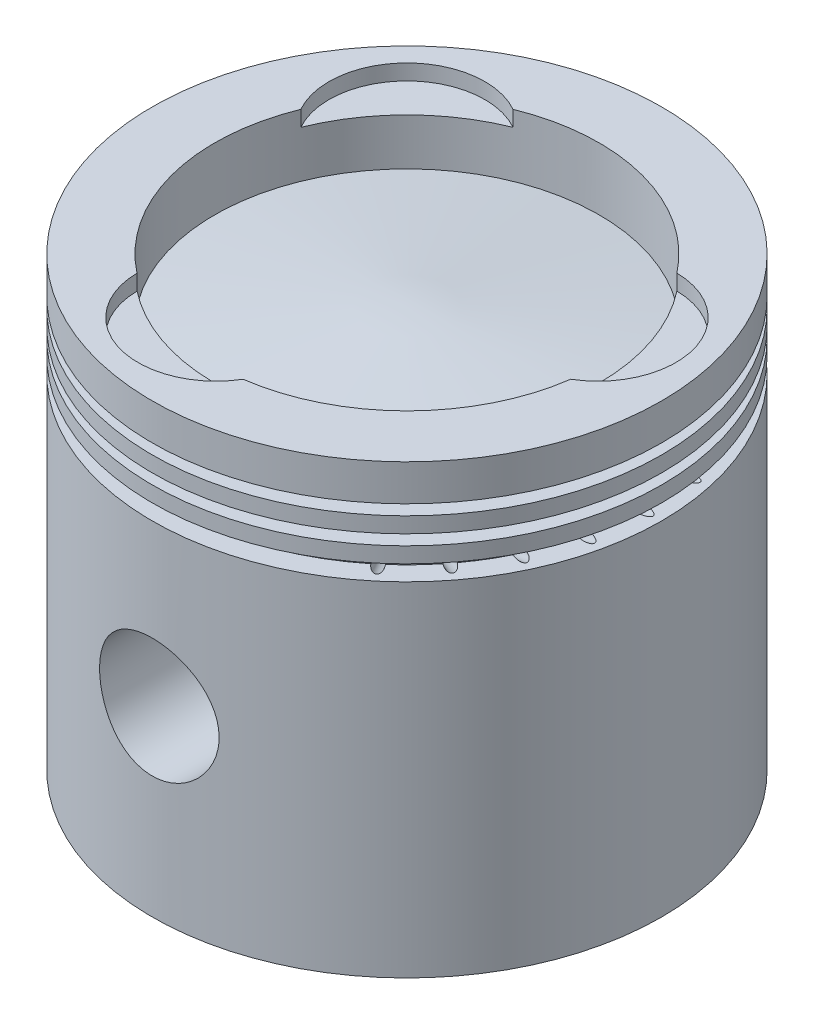
SolidWorks part; units mm, degrees
ref_plane "Front Plane" through (0, 0, 0) normal (0, 0, 1) x (1, 0, 0)
ref_plane "Top Plane" through (0, 0, 0) normal (0, 1, 0) x (1, 0, 0)
ref_plane "Right Plane" through (0, 0, 0) normal (1, 0, 0) x (0, 0, -1)
sketch "Sketch1" plane through (0, 0, 0) normal (0, 0, 1) x (1, 0, 0)
  line L0 (-803.1024, 0) -> (39352.0158, 0) construction
  line L1 (49, 0) -> (49, 66)
  line L2 (0, -803.1024) -> (0, 39352.0158) construction
  line L3 (49, 66) -> (45, 66)
  line L20 (45, 66) -> (45, 69)
  line L21 (45, 69) -> (49, 69)
  line L22 (49, 69) -> (49, 72)
  line L23 (49, 72) -> (45, 72)
  line L24 (45, 72) -> (45, 74)
  line L25 (45, 74) -> (49, 74)
  line L26 (49, 74) -> (49, 77)
  line L27 (49, 77) -> (45, 77)
  line L28 (45, 77) -> (45, 79)
  line L29 (45, 79) -> (49, 79)
  line L30 (49, 79) -> (49, 86)
  line L31 (49, 86) -> (0, 86) construction
  line L32 (0, 86) -> (0, 0) construction
  line L33 (49, 86) -> (37, 86)
  line L34 (37, 86) -> (37, 74)
  line L36 (0, 74) -> (0, 0) construction
  line L37 (0, 63) -> (39, 63)
  line L38 (39, 63) -> (39, 55.3502)
  line L39 (39, 55.3502) -> (20, 52)
  line L40 (20, 52) -> (20, 18)
  line L41 (20, 18) -> (45, 13.5918)
  line L42 (45, 13.5918) -> (45, 3)
  line L43 (45, 3) -> (42, 3)
  line L44 (42, 3) -> (42, 0)
  line L45 (42, 0) -> (0, 0) construction
  line L46 (49, 0) -> (42, 0)
  line L49 (37, 74) -> (0, 78)
  line L51 (0, 78) -> (0, 63)
  point P4 (45, 67.5)
  point P23 (49, 82.5)
  point P27 (20, 35)
  dimension "D1" = 66
  dimension "D2" = 69
  dimension "D3" = 72
  dimension "D4" = 74
  dimension "D5" = 77
  dimension "D6" = 79
  dimension "D7" = 86
  dimension "D8" = 49
  dimension "D9" = 45
  dimension "D10" = 45
  dimension "D11" = 45
  dimension "D12" = 4
  dimension "D13" = 4
  dimension "D14" = 4
  dimension "D15" = 8
  dimension "D16" = 12
  dimension "D17" = 35
  dimension "D18" = 17
  dimension "D19" = 17
  dimension "D20" = 63
  dimension "D21" = 100
  dimension "D22" = 39
  dimension "D23" = 20
  dimension "D24" = 100
  dimension "D25" = 45
  dimension "D26" = 42
  dimension "D27" = 3
  dimension "D28" = 12
revolve "Revolve2" add sketch "Sketch1" angle 360 about L2
sketch "Sketch3" plane through (0, 86, 0) normal (0, 1, 0) x (1, 0, 0)
  line L0 (0, 0) -> (35355.3391, 35355.3391) construction
  line L1 (-47.3, 0) -> (47.3, 0) construction
  line L2 (0, 0) -> (35355.3391, -35355.3391) construction
  circle A2 centre (0, 0) radius 45 construction
  circle A3 centre (-21.2132, 21.2132) radius 15
  dimension "D3" = 90
  dimension "D4" = 30
  dimension "D5" = 30
  dimension "D1" = 45
  dimension "D2" = 45
extrude "Cut-Extrude1" cut sketch "Sketch3" against normal blind 3
pattern_circular "CirPattern1" count 3 over 360 about axis through (0, 0, 0) along (0, 1, 0) of "Cut-Extrude1"
fillet "Fillet1" radius 4 2 edges at (39, 55.3502, 0) (39, 63, 0)
fillet "Fillet2" radius 3 2 edges at (20, 18, 0) (20, 52, 0)
fillet "Fillet3" radius 4 2 edges at (45, 3, 0) (45, 13.5918, 0)
sketch "Sketch4" plane through (0, 0, 0) normal (0, 0, 1) x (1, 0, 0)
  line L0 (0, -47.3) -> (0, 47.3) construction
  line L1 (53.9, 0) -> (-53.9, 0) construction
  circle A0 centre (0, 35) radius 11.5
  dimension "D1" = 35
  dimension "D2" = 23
extrude "Cut-Extrude2" cut sketch "Sketch4" against normal mid plane 119
sketch "Sketch5" plane through (0, 0, 0) normal (0, 0, 1) x (1, 0, 0)
  line L0 (47.1294, 66.9929) -> (34.4411, 61.0763)
  line L1 (45, 66) -> (45, 69) construction
  line L2 (-49, 0) -> (49, 0) construction
  dimension "D1" = 115
  dimension "D2" = 14
  dimension "D3" = 66.9929
sweep "Cut-Sweep1" cut path "Sketch5" circular profile diameter 2 parameters "D3"=2
pattern_circular "CirPattern2" count 5 every 12.5 about axis through (0, -803.1024, 0) along (0, -1, 0) of "Cut-Sweep1"
mirror "Mirror2" about plane through (0, 0, 0) normal (0, 0, 1) of "CirPattern2"
